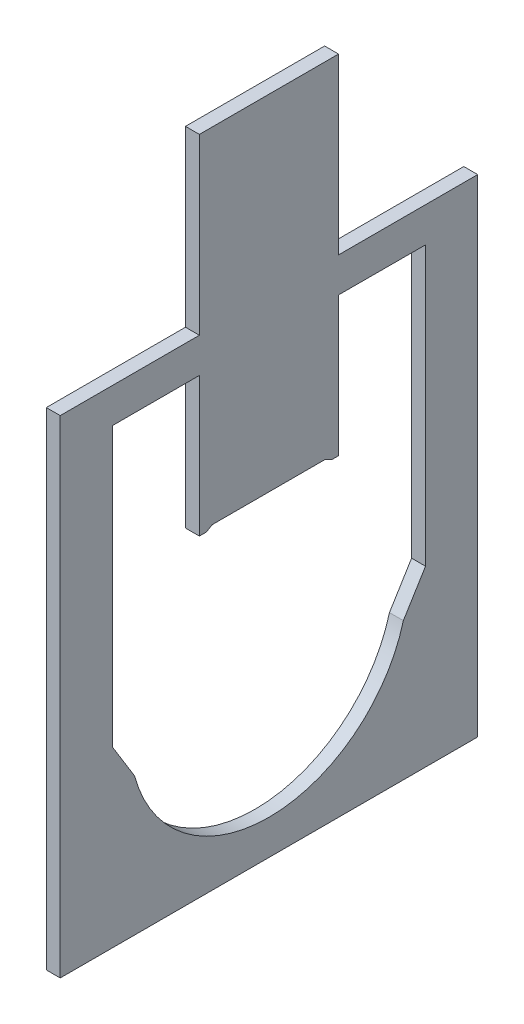
SolidWorks part; units mm, degrees
ref_plane "Front Plane" through (0, 0, 0) normal (0, 0, 1) x (1, 0, 0)
ref_plane "Top Plane" through (0, 0, 0) normal (0, 1, 0) x (1, 0, 0)
ref_plane "Right Plane" through (0, 0, 0) normal (1, 0, 0) x (0, 0, -1)
sketch "Sketch1" plane through (0, 0, 0) normal (1, 0, 0) x (0, 0, -1)
  line L0 (-29.3185, -50.1764) -> (-32.5, -45) construction
  line L5 (-29.3185, -50.1764) -> (-32.5, -45)
  line L6 (12.5, -45) -> (9.3185, -50.1764) construction
  line L7 (12.5, -45) -> (9.3185, -50.1764)
  line L8 (-1.866, -24.5) -> (-1, -25) construction
  line L9 (-20, -25) -> (-19, -25) construction
  line L10 (-19, -25) -> (-18.134, -24.5) construction
  line L11 (-18.134, -24.5) -> (-1.866, -24.5) construction
  line L12 (-1.866, -24.5) -> (-1, -25)
  line L13 (-20, -25) -> (-19, -25)
  line L14 (-19, -25) -> (-18.134, -24.5)
  line L15 (-18.134, -24.5) -> (-1.866, -24.5)
  line L16 (0, 25) -> (0, -25) construction
  line L17 (0, 25) -> (0, -25)
  line L18 (0, -25) -> (-1, -25)
  line L19 (-20, 25) -> (-20, -25) construction
  line L20 (-20, 25) -> (-20, -25)
  line L21 (-34.55, -5) -> (-19.95, -5) construction
  line L22 (-32.5, -5) -> (-19.95, -5)
  line L23 (-32.5, -45) -> (-32.5, -5)
  line L24 (12.5, -45) -> (12.5, -5)
  line L26 (12.5, -5) -> (0, -4.9816)
  line L27 (-20, 25) -> (0, 25)
  line L28 (0, 0) -> (20, 0)
  line L29 (20, 0) -> (20, -70)
  line L30 (20, -70) -> (-40, -70)
  line L31 (-40, -70) -> (-40, 0)
  line L32 (-40, 0) -> (-20, 0)
  arc A0 (-29.3185, -50.1764) -> (9.3185, -50.1764) centre (-10, -45) ccw construction
  arc A1 (-29.3185, -50.1764) -> (9.3185, -50.1764) centre (-10, -45) ccw
  dimension "D1" = 20
  dimension "D2" = 70
extrude "Boss-Extrude1" add sketch "Sketch1" along normal blind 2 contours A1 L5 L23 L22 L20 L32 L31 L30 L29 L28 L17 L26 L24 L7 | L27 L20 L13 L14 L15 L12 L18 L17 region at (0, -65.922, 10) region at (0, 0.2139, 10)
